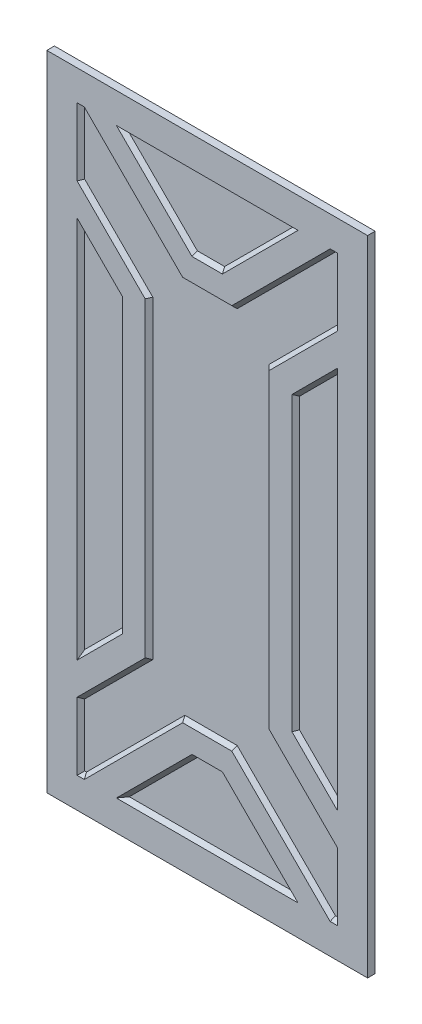
SolidWorks part; units mm, degrees
ref_plane "Plan de face" through (0, 0, 0) normal (0, 0, 1) x (1, 0, 0)
ref_plane "Plan de dessus" through (0, 0, 0) normal (0, 1, 0) x (1, 0, 0)
ref_plane "Plan de droite" through (0, 0, 0) normal (1, 0, 0) x (0, 0, -1)
sketch "Esquisse1" plane through (0, 0, 0) normal (0, 0, 1) x (1, 0, 0)
  line L1 (0, 0) -> (424, 0)
  line L2 (0, 0) -> (0, 850)
  line L3 (0, 850) -> (424, 850)
  line L4 (424, 0) -> (424, 850)
  dimension "D1" = 850
  dimension "D2" = 424
extrude "Boss.-Extru.1" add sketch "Esquisse1" along normal blind 10
sketch "Esquisse2" plane through (0, 0, 10) normal (0, 0, 1) x (1, 0, 0)
  line L0 (179.4975, 680) -> (130, 630.5025) construction
  line L1 (100, 231.9239) -> (100, 618.0761)
  line L2 (100, 618.0761) -> (40, 678.0761)
  line L3 (191.9239, 710) -> (232.0761, 710)
  line L4 (212, 810) -> (212, 40) construction
  line L5 (384, 425) -> (40, 425) construction
  line L6 (40, 810) -> (40, 720.5025)
  line L7 (40, 720.5025) -> (130, 630.5025)
  line L8 (40, 810) -> (40, 40)
  line L9 (40, 40) -> (384, 40)
  line L10 (384, 40) -> (384, 810)
  line L11 (384, 810) -> (40, 810)
  line L12 (40, 810) -> (40, 40) construction
  line L13 (40, 40) -> (384, 40) construction
  line L14 (384, 40) -> (384, 810) construction
  line L15 (384, 810) -> (40, 810) construction
  line L16 (130, 630.5025) -> (130, 219.4975)
  line L17 (40, 810) -> (49.4975, 810)
  line L18 (49.4975, 810) -> (179.4975, 680)
  line L19 (244.5025, 680) -> (179.4975, 680)
  line L20 (332.0761, 810) -> (91.9239, 810)
  line L21 (91.9239, 810) -> (191.9239, 710)
  line L22 (294, 630.5025) -> (294, 219.4975)
  line L23 (40, 678.0761) -> (40, 171.9239)
  line L24 (324, 231.9239) -> (324, 618.0761)
  line L25 (130, 630.5025) -> (130, 680) construction
  line L26 (130, 680) -> (179.4975, 680) construction
  line L27 (324, 618.0761) -> (384, 678.0761)
  line L28 (384, 678.0761) -> (384, 171.9239)
  line L29 (384, 720.5025) -> (294, 630.5025)
  line L30 (384, 810) -> (384, 720.5025)
  line L31 (384, 810) -> (374.5025, 810)
  line L32 (374.5025, 810) -> (244.5025, 680)
  line L33 (332.0761, 810) -> (232.0761, 710)
  line L34 (100, 231.9239) -> (40, 171.9239)
  line L35 (40, 129.4975) -> (130, 219.4975)
  line L36 (384, 40) -> (374.5025, 40)
  line L37 (384, 40) -> (384, 129.4975)
  line L38 (40, 40) -> (40, 129.4975)
  line L39 (40, 40) -> (49.4975, 40)
  line L40 (332.0761, 40) -> (91.9239, 40)
  line L41 (191.9239, 140) -> (232.0761, 140)
  line L42 (244.5025, 170) -> (179.4975, 170)
  line L43 (91.9239, 40) -> (191.9239, 140)
  line L44 (49.4975, 40) -> (179.4975, 170)
  line L45 (332.0761, 40) -> (232.0761, 140)
  line L46 (374.5025, 40) -> (244.5025, 170)
  line L47 (384, 129.4975) -> (294, 219.4975)
  line L48 (324, 231.9239) -> (384, 171.9239)
  point P20 (212, 680)
  point P23 (294, 425)
  point P31 (212, 710)
  point P33 (100, 425)
  point P34 (130, 425)
  point P47 (324, 425)
  dimension "D2" = 90
  dimension "D3" = 130
  dimension "D4" = 70
  dimension "D5" = 45
  dimension "D6" = 30
  dimension "D7" = 30
  dimension "D8" = 30
  dimension "D9" = 30
  dimension "D1" = 40
extrude "Enlèv. mat.-Extru.1" cut sketch "Esquisse2" against normal blind 5
chamfer "Chanfrein1" distance 5 angle 45 36 edges at (212, 40, 5) (141.9239, 90, 5) (212, 140, 5) (282.0761, 90, 5) (40, 425, 5) (70, 648.0761, 5) (100, 425, 5) (70, 201.9239, 5) (384, 425, 5) (354, 201.9239, 5) (324, 425, 5) (354, 648.0761, 5) (114.4975, 745, 5) (212, 680, 5) (309.5025, 745, 5) (379.2513, 810, 5) (384, 765.2513, 5) (339, 675.5025, 5) (294, 425, 5) (339, 174.4975, 5) (384, 84.7487, 5) (379.2513, 40, 5) (309.5025, 105, 5) (212, 170, 5) (114.4975, 105, 5) (44.7487, 40, 5) (40, 84.7487, 5) (85, 174.4975, 5) (130, 425, 5) (85, 675.5025, 5) (40, 765.2513, 5) (44.7487, 810, 5) (212, 810, 5) (282.0761, 760, 5) (212, 710, 5) (141.9239, 760, 5)
